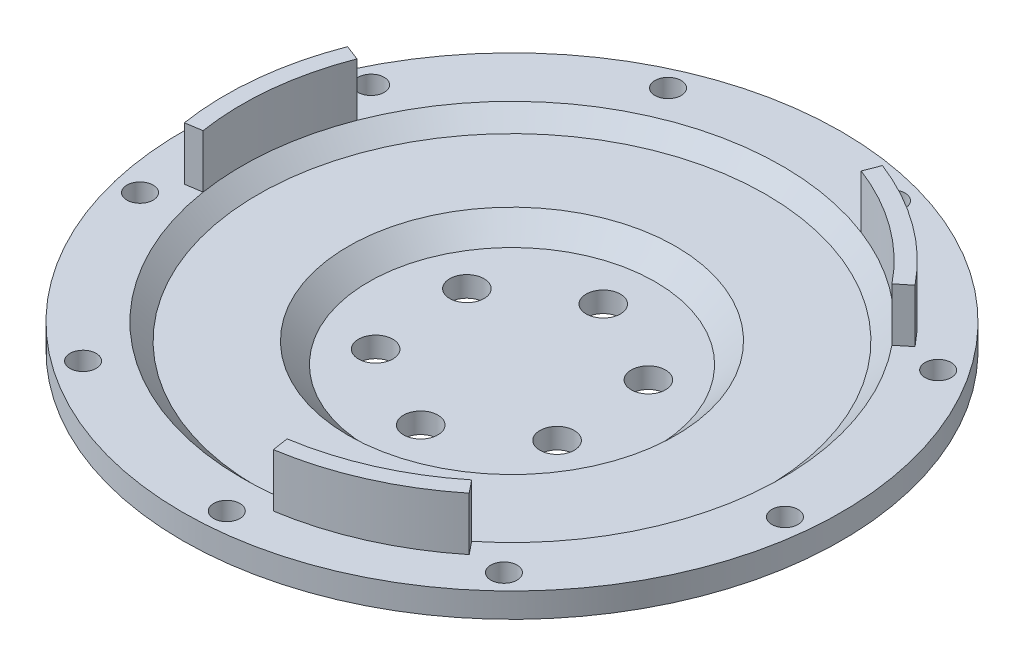
SolidWorks part; units mm, degrees
ref_plane "前视基准面" through (0, 0, 0) normal (0, 0, 1) x (1, 0, 0)
ref_plane "上视基准面" through (0, 0, 0) normal (0, 1, 0) x (1, 0, 0)
ref_plane "右视基准面" through (0, 0, 0) normal (1, 0, 0) x (0, 0, -1)
sketch "草图3" plane through (0, 0, 0) normal (0, 1, 0) x (1, 0, 0)
  line L0 (-2.8856, 36.1038) -> (-0.4473, 0.6876) construction
  arc A0 (36.6394, 4.8689) -> (34.9909, 2.7814) centre (36.9875, 2.8994) ccw
  arc A1 (36.6394, 4.8689) -> (38.264, 7.1686) centre (36.2914, 6.8384) ccw
  arc A2 (38.264, 7.1686) -> (37.647, 10.1422) centre (-0.4473, 0.6876) ccw
  arc A3 (37.647, 10.1422) -> (36.802, 13.0591) centre (-0.4473, 0.6876) ccw
  arc A4 (36.802, 13.0591) -> (34.2907, 14.3324) centre (34.9039, 12.4288) ccw
  arc A5 (31.8575, 15.4068) -> (34.2907, 14.3324) centre (33.6774, 16.2361) ccw
  arc A6 (31.8575, 15.4068) -> (31.274, 16.6253) centre (-0.4473, 0.6876) ccw
  arc A7 (31.1201, 17.0414) -> (31.274, 16.6253) centre (33.0612, 17.5231) ccw
  arc A8 (32.0519, 19.2498) -> (31.1201, 17.0414) centre (33.0612, 17.5231) ccw
  arc A9 (32.0519, 19.2498) -> (33.3332, 22.2864) centre (30.6641, 21.624) ccw
  arc A10 (33.3332, 22.2864) -> (28.9874, 23.8037) centre (30.6641, 21.624) ccw
  arc A11 (26.2631, 24.0715) -> (28.9874, 23.8037) centre (27.7679, 25.3889) ccw
  arc A12 (26.2631, 24.0715) -> (13.6082, 33.2866) centre (-0.4473, 0.6876) ccw
  arc A13 (13.2227, 33.5064) -> (13.6082, 33.2866) centre (14.4, 35.1232) ccw
  arc A14 (12.517, 35.7971) -> (13.2227, 33.5064) centre (14.4, 35.1232) ccw
  arc A15 (12.517, 35.7971) -> (11.5466, 38.9469) centre (9.9278, 36.7238) ccw
  arc A16 (11.5466, 38.9469) -> (7.2423, 37.3158) centre (9.9278, 36.7238) ccw
  arc A17 (4.9832, 35.7698) -> (7.2423, 37.3158) centre (5.2892, 37.7463) ccw
  arc A18 (4.9832, 35.7698) -> (-10.6344, 34.6946) centre (-0.4473, 0.6876) ccw
  arc A19 (-11.071, 34.6152) -> (-10.6344, 34.6946) centre (-11.2084, 36.6104) ccw
  arc A20 (-13.084, 35.9163) -> (-11.071, 34.6152) centre (-11.2084, 36.6104) ccw
  arc A21 (-13.084, 35.9163) -> (-15.852, 37.7054) centre (-15.6631, 34.9619) ccw
  arc A22 (-15.852, 37.7054) -> (-18.1008, 33.6892) centre (-15.6631, 34.9619) ccw
  arc A23 (-18.8377, 31.0528) -> (-18.1008, 33.6892) centre (-19.8737, 32.7635) ccw
  arc A24 (-18.8377, 31.0528) -> (-30.1103, 20.1903) centre (-0.4473, 0.6876) ccw
  arc A25 (-30.3937, 19.8488) -> (-30.1103, 20.1903) centre (-31.7815, 21.289) ccw
  arc A26 (-32.7722, 19.5516) -> (-30.3937, 19.8488) centre (-31.7815, 21.289) ccw
  arc A27 (-32.7722, 19.5516) -> (-36.0426, 19.1429) centre (-34.1344, 17.1627) ccw
  arc A28 (-36.0426, 19.1429) -> (-35.1837, 14.6208) centre (-34.1344, 17.1627) ccw
  arc A29 (-34.0535, 12.1276) -> (-35.1837, 14.6208) centre (-35.9468, 12.7721) ccw
  arc A30 (-34.0535, 12.1276) -> (-35.7065, -3.4395) centre (-0.4473, 0.6876) ccw
  arc A31 (-35.7042, -3.8832) -> (-35.7065, -3.4395) centre (-37.693, -3.672) ccw
  arc A32 (-37.3351, -5.6398) -> (-35.7042, -3.8832) centre (-37.693, -3.672) ccw
  arc A33 (-37.3351, -5.6398) -> (-39.5777, -8.055) centre (-36.8431, -8.3454) ccw
  arc A34 (-39.5777, -8.055) -> (-36.0129, -10.9671) centre (-36.8431, -8.3454) ccw
  arc A35 (-33.5446, -12.1505) -> (-36.0129, -10.9671) centre (-35.4092, -12.8738) ccw
  arc A36 (-33.5446, -12.1505) -> (-24.8046, -25.1382) centre (-0.4473, 0.6876) ccw
  arc A37 (-24.5175, -25.4766) -> (-24.8046, -25.1382) centre (-26.1768, -26.5932) ccw
  arc A38 (-24.6378, -27.8705) -> (-24.5175, -25.4766) centre (-26.1768, -26.5932) ccw
  arc A39 (-24.6378, -27.8705) -> (-24.8033, -31.1622) centre (-22.5218, -29.6268) ccw
  arc A40 (-24.8033, -31.1622) -> (-20.2006, -31.1016) centre (-22.5218, -29.6268) ccw
  arc A41 (-17.5491, -30.4215) -> (-20.2006, -31.1016) centre (-18.5126, -32.1741) ccw
  arc A42 (-17.5491, -30.4215) -> (-2.5055, -34.7527) centre (-0.4473, 0.6876) ccw
  arc A43 (-2.0681, -34.8274) -> (-2.5055, -34.7527) centre (-2.6215, -36.7493) ccw
  arc A44 (-0.6215, -36.7386) -> (-2.0681, -34.8274) centre (-2.6215, -36.7493) ccw
  arc A45 (-0.6215, -36.7386) -> (1.3676, -39.3665) centre (2.1284, -36.7238) ccw
  arc A46 (1.3676, -39.3665) -> (4.8545, -36.3616) centre (2.1284, -36.7238) ccw
  arc A47 (6.4486, -34.1362) -> (4.8545, -36.3616) centre (6.8371, -36.0981) ccw
  arc A48 (6.4486, -34.1362) -> (20.7566, -27.7842) centre (-0.4473, 0.6876) ccw
  arc A49 (21.1397, -27.5603) -> (20.7566, -27.7842) centre (21.9512, -29.3883) ccw
  arc A50 (23.4763, -28.0945) -> (21.1397, -27.5603) centre (21.9512, -29.3883) ccw
  arc A51 (23.4763, -28.0945) -> (26.6893, -28.829) centre (25.5735, -26.3156) ccw
  arc A52 (26.6893, -28.829) -> (27.4289, -24.2858) centre (25.5735, -26.3156) ccw
  arc A53 (27.2196, -21.5564) -> (27.4289, -24.2858) centre (28.7782, -22.8096) ccw
  arc A54 (27.2196, -21.5564) -> (34.0972, -7.4935) centre (-0.4473, 0.6876) ccw
  arc A55 (34.2467, -7.0757) -> (34.0972, -7.4935) centre (36.0433, -7.9544) ccw
  arc A56 (36.3801, -5.983) -> (34.2467, -7.0757) centre (36.0433, -7.9544) ccw
  arc A57 (36.3801, -5.983) -> (39.3135, -4.4804) centre (36.8431, -3.2722) ccw
  arc A58 (39.3135, -4.4804) -> (36.9597, -0.5247) centre (36.8431, -3.2722) ccw
  arc A59 (35.0449, 1.4316) -> (36.9597, -0.5247) centre (37.0445, 1.4735) ccw
  arc A60 (35.0449, 1.4316) -> (34.9909, 2.7814) centre (-0.4473, 0.6876) ccw
  circle A61 centre (-0.4473, 0.6876) radius 12 construction
  circle A62 centre (-1.2715, 12.6593) radius 2.1
  circle A63 centre (9.5084, 7.3873) radius 2.1
  circle A64 centre (10.3326, -4.5844) radius 2.1
  circle A65 centre (0.377, -11.284) radius 2.1
  circle A66 centre (-10.4029, -6.012) radius 2.1
  circle A67 centre (-11.2271, 5.9596) radius 2.1
  circle A68 centre (-0.4473, 0.6876) radius 40.25
  circle A69 centre (-15.6631, 34.9619) radius 1.6
  circle A70 centre (9.9278, 36.7238) radius 1.6
  circle A71 centre (30.6641, 21.624) radius 1.6
  circle A72 centre (36.8431, -3.2722) radius 1.6
  circle A73 centre (25.5735, -26.3156) radius 1.6
  circle A74 centre (2.1284, -36.7238) radius 1.6
  circle A75 centre (-22.5218, -29.6268) radius 1.6
  circle A76 centre (-36.8431, -8.3454) radius 1.6
  circle A77 centre (-34.1344, 17.1627) radius 1.6
  circle A78 centre (-0.4473, 0.6876) radius 17.5
  point P138 (-0.4473, 0.6876)
  point P158 (-0.4473, 0.6876)
  dimension "D1" = 35.5
  dimension "D2" = 24
  dimension "D3" = 4.2
  dimension "D4" = 35.5
  dimension "D5" = 80.5
  dimension "D6" = 3.2
  dimension "D8" = 35
  dimension "D9" = 6
  dimension "D7" = 9
extrude "凸台-拉伸1" add sketch "草图3" along normal blind 3 from offset 2 contours A59 A60 A0 A1 A2 A3 A4 A5 A6 A7 A8 A9 A10 A11 A12 A13 A14 A15 A16 A17 A18 A19 A20 A21 A22 A23 A24 A25 A26 A27 A28 A29 A30 A31 A32 A33 A34 A35 A36 A37 A38 A39 A40 A41 A42 | A34 A68 A40 A39 A38 A37 A36 A35 | A28 A68 A34 A33 A32 A31 A30 A29 | A22 A68 A28 A27 A26 A25 A24 A23 | A16 A68 A22 A21 A20 A19 A18 A17 | A10 A68 A16 A15 A14 A13 A12 A11 | A58 A68 A10 A9 A8 A7 A6 A5 A4 A3 A2 A1 A0 A60 A59 | A52 A68 A58 A57 A56 A55 A54 A53 | A46 A68 A52 A51 A50 A49 A48 A47 | A40 A68 A46 A45 A44 A43 A42 A41 region at (38.1546, 0, -5.5222) region at (34.5403, 0, -4.8319) region at (33.2456, 0, 15.7903) region at (14.7712, 0, 33.5925) region at (-10.8241, 0, 35.3547) region at (21.631, 0, -31.0072) region at (-31.564, 0, 20.2523) region at (-3.0234, 0, -38.1054) region at (-37.744, 0, -4.6481) region at (-26.4724, 0, -27.6954)
extrude "凸台-拉伸3" add sketch "草图3<4>" along normal blind 2.5 contours A78 A62 A63 A64 A65 A66 A67 region at (-0.4473, 0, -0.6876)
sketch "草图3<4>" plane through (0, 0, 0) normal (0, 1, 0) x (1, 0, 0) same geometry as "草图3"
chamfer "倒角1" distance 3 angle 45 1 edges at (-0.4473, 2, 16.8124)
chamfer "倒角4" distance 2.5 angle 45 1 edges at (-0.4473, 5, 16.8124)
sketch "草图4" plane through (0, 5, 0) normal (0, 1, 0) x (1, 0, 0)
  circle A0 centre (-0.4473, 0.6876) radius 33
  circle A1 centre (-0.4473, 0.6876) radius 40.25
  circle A2 centre (-0.4473, 0.6876) radius 40.25
  circle A3 centre (-36.8431, -8.3454) radius 1.6 construction
  circle A4 centre (-22.5218, -29.6268) radius 1.6 construction
  circle A5 centre (2.1284, -36.7238) radius 1.6 construction
  circle A6 centre (25.5735, -26.3156) radius 1.6 construction
  circle A7 centre (36.8431, -3.2722) radius 1.6 construction
  circle A8 centre (30.6641, 21.624) radius 1.6 construction
  circle A9 centre (9.9278, 36.7238) radius 1.6 construction
  circle A10 centre (-15.6631, 34.9619) radius 1.6 construction
  circle A11 centre (-34.1344, 17.1627) radius 1.6 construction
  circle A12 centre (-36.8431, -8.3454) radius 1.6
  circle A13 centre (-22.5218, -29.6268) radius 1.6
  circle A14 centre (2.1284, -36.7238) radius 1.6
  circle A15 centre (25.5735, -26.3156) radius 1.6
  circle A16 centre (36.8431, -3.2722) radius 1.6
  circle A17 centre (30.6641, 21.624) radius 1.6
  circle A18 centre (9.9278, 36.7238) radius 1.6
  circle A19 centre (-15.6631, 34.9619) radius 1.6
  circle A20 centre (-34.1344, 17.1627) radius 1.6
  dimension "D2" = 66
  dimension "D1" = 0
extrude "凸台-拉伸4" add sketch "草图4" along normal blind 2
extrude "切除-拉伸4" cut sketch "草图4<4>" against normal blind 12 from offset 1 offset against normal yes
sketch "草图4<4>" plane through (0, 5, 0) normal (0, 1, 0) x (1, 0, 0) same geometry as "草图4"
chamfer "倒角5" distance 2 angle 45 1 edges at (-0.4473, 5, 32.3124)
chamfer "倒角8" distance 2 angle 45 1 edges at (-0.4473, 2, 32.3124)
sketch "草图5" plane through (0, 7, 0) normal (0, 1, 0) x (1, 0, 0)
  line L0 (21.5497, -26.5361) -> (20.2928, -24.9805)
  line L1 (12.1307, 33.3495) -> (11.4119, 31.4831)
  line L2 (25.2208, 21.4277) -> (26.7765, 22.6846)
  line L3 (4.6801, -31.9116) -> (4.9908, -33.8873)
  line L4 (-35.0222, -4.7505) -> (-33.0465, -4.4397)
  line L5 (-31.2427, 12.5468) -> (-33.1091, 13.2656)
  line L6 (-0.4473, 0.6876) -> (9.9278, 36.7238)
  circle A0 centre (-0.4473, 0.6876) radius 33 construction
  arc A1 (4.6801, -31.9116) -> (20.2928, -24.9805) centre (-0.4473, 0.6876) ccw
  arc A3 (25.2208, 21.4277) -> (11.4119, 31.4831) centre (-0.4473, 0.6876) ccw
  circle A4 centre (9.9278, 36.7238) radius 1.6 construction
  circle A5 centre (9.9278, 36.7238) radius 1.6
  arc A8 (26.7765, 22.6846) -> (12.1307, 33.3495) centre (-0.4473, 0.6876) ccw
  circle A9 centre (-0.4473, 0.6876) radius 35 construction
  circle A10 centre (-0.4473, 0.6876) radius 33 construction
  arc A11 (4.9908, -33.8873) -> (21.5497, -26.5361) centre (-0.4473, 0.6876) ccw
  arc A12 (-31.2427, 12.5468) -> (-33.0465, -4.4397) centre (-0.4473, 0.6876) ccw
  arc A13 (-33.1091, 13.2656) -> (-35.0222, -4.7505) centre (-0.4473, 0.6876) ccw
  point P23 (-0.4473, 0.6876)
  dimension "D3" = 2
  dimension "D2" = 2
  dimension "D4" = 2
  dimension "D5" = 30
  dimension "D6" = 5
  dimension "D1" = 3
extrude "凸台-拉伸5" add sketch "草图5" along normal blind 6.5 contours L2 A8 L1 | L3 A11 L0 A8 | L5 A13 L4 A8 region at (13.1953, 7, 30.0428) region at (19.3448, 7, -27.8677) region at (-33.8819, 7, -4.238)
